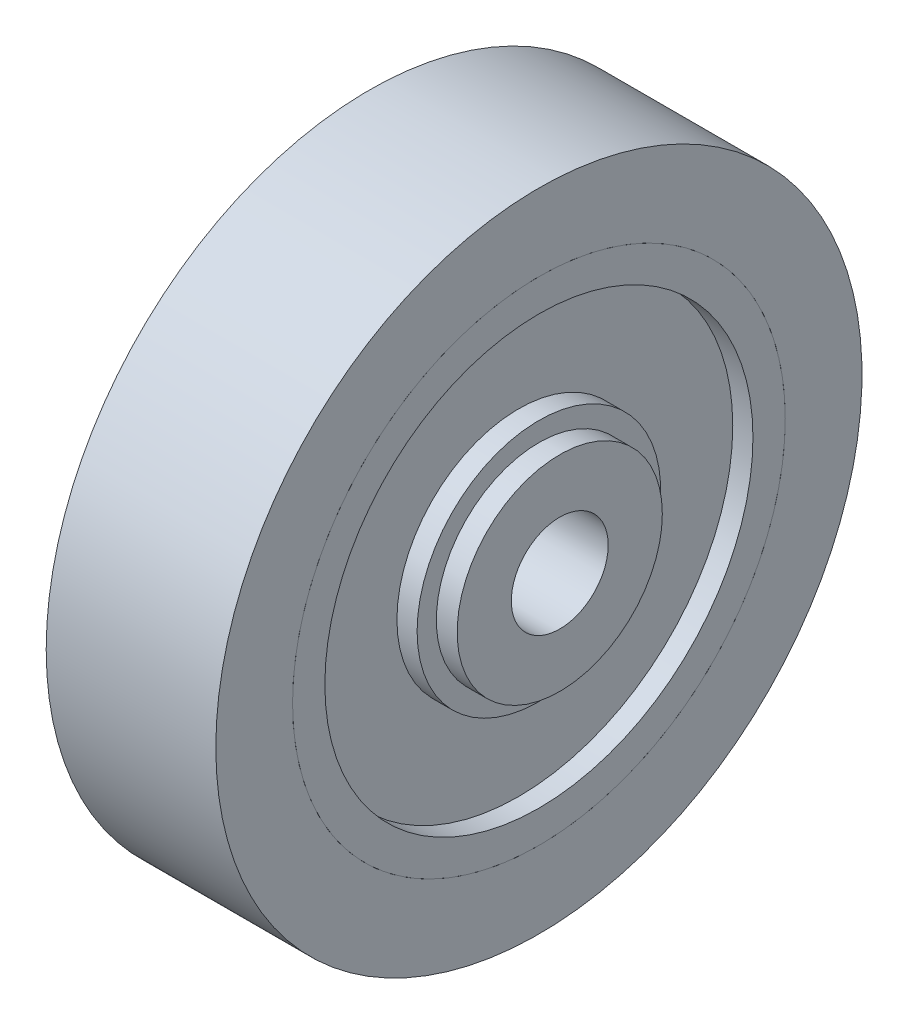
SolidWorks part; units mm, degrees
other "Tire"
other "Rim"
other "Hub"
other "Clip"
ref_plane "Front Plane" through (0, 0, 0) normal (0, 0, 1) x (1, 0, 0)
ref_plane "Top Plane" through (0, 0, 0) normal (0, 1, 0) x (1, 0, 0)
ref_plane "Right Plane" through (0, 0, 0) normal (1, 0, 0) x (0, 0, -1)
sketch "Sketch1" plane through (0, 0, 0) normal (1, 0, 0) x (0, 0, -1)
  line L0 (0, 15.25) -> (0, 20) construction
  circle A0 centre (0, 0) radius 20
  circle A1 centre (0, 0) radius 15.25
  circle A2 centre (0, 0) radius 20 construction
  dimension "D2" = 4.75
extrude "Boss-Extrude1" add sketch "Sketch1" along normal blind 10.5
ref_plane "Plane4" through (0, 0, 0) normal (-1, 0, 0) x (0, 0, 1)
sketch "Sketch2" plane through (10.5, 0, 0) normal (1, 0, 0) x (0, 0, -1)
  circle A0 centre (0, 0) radius 15.25 construction
  circle A1 centre (0, 0) radius 15.25
  circle A2 centre (0, 0) radius 13.25
  dimension "D1" = 2
extrude "Boss-Extrude2" add sketch "Sketch2" against normal up to surface (10.5 mm away) separate body up to face at (0, 0, -20)
ref_plane "Mid-Plane" through (5.25, 0, 0) normal (1, 0, 0) x (0, 0, -1)
ref_axis "Axis1" through (0, 0, 0) along (1, 0, 0)
sketch "Sketch3" plane through (5.25, 0, 0) normal (1, 0, 0) x (0, 0, -1)
  line L1 (7.3323, 0) -> (3.6662, 6.35)
  line L2 (3.6662, 6.35) -> (-3.6662, 6.35)
  line L3 (-3.6662, 6.35) -> (-7.3323, 0)
  line L4 (-7.3323, 0) -> (-3.6662, -6.35)
  line L5 (-3.6662, -6.35) -> (3.6662, -6.35)
  line L6 (3.6662, -6.35) -> (7.3323, 0)
  circle A0 centre (0, 0) radius 6.35 construction
  circle A1 centre (0, 0) radius 13.25 construction
  circle A2 centre (0, 0) radius 13.25
  dimension "D1" = 12.7
extrude "Boss-Extrude3" add sketch "Sketch3" along normal offset from surface 1.25 and the other way offset from surface 1.25 up to face at (10.5, 0, -13.25) other way up to face at (0, 0, -15.25)
sketch "Sketch4" plane through (1.25, 0, 0) normal (-1, 0, 0) x (0, 0, 1)
  circle A0 centre (0, 0) radius 7.625
  circle A1 centre (0, 0) radius 3
  dimension "D1" = 15.25
  dimension "D2" = 6
extrude "Boss-Extrude4" add sketch "Sketch4" along normal up to surface (1.25 mm away) separate body up to face at (0, 0, -15.25)
sketch "Sketch5" plane through (1.25, 0, 0) normal (1, 0, 0) x (0, 0, -1)
  line L0 (-7.3323, 0) -> (-3.6662, 6.35) construction
  line L1 (-3.6662, 6.35) -> (3.6662, 6.35) construction
  line L2 (3.6662, 6.35) -> (7.3323, 0) construction
  line L3 (7.3323, 0) -> (3.6662, -6.35) construction
  line L4 (3.6662, -6.35) -> (-3.6662, -6.35) construction
  line L5 (-3.6662, -6.35) -> (-7.3323, 0) construction
  line L6 (-7.3323, 0) -> (-3.6662, 6.35)
  line L7 (-3.6662, 6.35) -> (3.6662, 6.35)
  line L8 (3.6662, 6.35) -> (7.3323, 0)
  line L9 (7.3323, 0) -> (3.6662, -6.35)
  line L10 (3.6662, -6.35) -> (-3.6662, -6.35)
  line L11 (-3.6662, -6.35) -> (-7.3323, 0)
  circle A0 centre (0, 0) radius 3 construction
  circle A1 centre (0, 0) radius 3
extrude "Boss-Extrude5" add sketch "Sketch5" along normal up to surface (8 mm away) up to face at (9.25, 0, 0)
sketch "Sketch6" plane through (9.25, 0, 0) normal (1, 0, 0) x (0, 0, -1)
  circle A0 centre (0, 0) radius 3 construction
  circle A1 centre (0, 0) radius 3
  circle A2 centre (0, 0) radius 5.94
  dimension "D1" = 11.88
extrude "Boss-Extrude6" add sketch "Sketch6" along normal up to surface (1.25 mm away) up to face at (10.5, 0, -13.25)
sketch "Sketch7" plane through (10.5, 0, 0) normal (1, 0, 0) x (0, 0, -1)
  line L0 (3.6662, -6.35) -> (7.3323, 0) construction
  circle A0 centre (0, 0) radius 6.35
  circle A1 centre (0, 0) radius 3 construction
  circle A2 centre (0, 0) radius 3
extrude "Boss-Extrude7" add sketch "Sketch7" along normal blind 1.29
ref_plane "Plane2" through (0, 0, 0) normal (0, 1, 0) x (1, 0, 0)
sketch "Sketch8" plane through (0, 6.35, 0) normal (0, 1, 0) x (1, 0, 0)
  line L0 (1.25, 0) -> (9.25, 0) construction
  line L1 (1.25, 3.6662) -> (1.25, -3.6662) construction
  line L2 (9.25, 3.6662) -> (9.25, -3.6662) construction
  circle A0 centre (5.25, 0) radius 1.5
  dimension "D1" = 3
extrude "Cut-Extrude1" cut sketch "Sketch8" against normal up to surface (6.35 mm away) up to plane "Plane2"
sketch "Sketch9" plane through (9.25, 0, 0) normal (1, 0, 0) x (0, 0, -1)
  circle A0 centre (0, 0) radius 5.94 construction
  circle A1 centre (0, 0) radius 5.94
  circle A2 centre (0, 0) radius 7.54
  dimension "D1" = 1.6
extrude "Boss-Extrude8" add sketch "Sketch9" along normal up to surface (1.25 mm away) separate body up to face at (10.5, 0, -5.94)
ref_plane "Plane3" through (0, 0, 0) normal (0, 0, 1) x (1, 0, 0)
